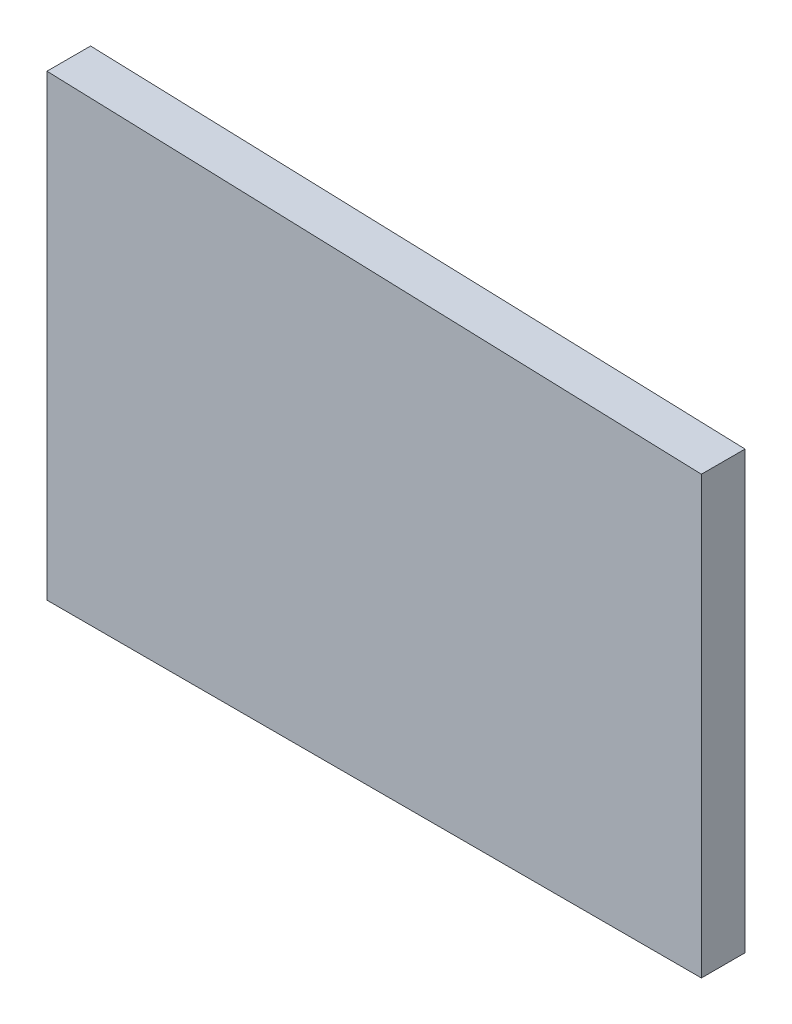
SolidWorks part; units mm, degrees
ref_plane "Ebene vorne" through (0, 0, 0) normal (0, 0, 1) x (1, 0, 0)
ref_plane "Ebene oben" through (0, 0, 0) normal (0, 1, 0) x (1, 0, 0)
ref_plane "Ebene rechts" through (0, 0, 0) normal (1, 0, 0) x (0, 0, -1)
sketch "Skizze1" plane through (0, 0, 0) normal (0, 0, 1) x (1, 0, 0)
  line L0 (0, 0) -> (0, 21)
  line L1 (0, 21) -> (30, 20)
  line L2 (30, 20) -> (30, 0)
  line L3 (30, 0) -> (0, 0)
  dimension "D1" = 30
  dimension "D2" = 20
  dimension "D3" = 21
  dimension "D4" = 90
  dimension "D5" = 90
extrude "Aufsatz-Linear austragen1" add sketch "Skizze1" along normal blind 2
sketch "Skizze2" plane through (0, 0, 2) normal (0, 0, 1) x (1, 0, 0)
  circle A0 centre (14.6667, 10.5) radius 18.0378
sketch "Skizze3" plane through (0, 0, 2) normal (0, 0, 1) x (1, 0, 0)
  line L0 (1, 1) -> (29, 1)
  line L1 (1, 1) -> (1, 19)
  line L2 (29, 1) -> (29, 19)
  line L3 (1, 19) -> (29, 19)
  line L4 (1, 1) -> (29, 19) construction
  line L5 (29, 1) -> (1, 19) construction
  line L6 (30, 0) -> (30, 20) construction
  line L7 (30, 20) -> (0, 21) construction
  point P1 (15, 10)
  point P8 (30, 10)
  point P11 (15, 20.5)
  dimension "D1" = 18
  dimension "D2" = 28
ref_point "SWASI_Vision_Point_1"
ref_point "SWASI_Vision_Point_1_helper"
ref_point "SWASI_Vision_Point_2"
ref_point "SWASI_Vision_Point_2_helper"
ref_point "SWASI_Vision_Point_3"
ref_point "SWASI_Vision_Point_3_helper"
ref_point "SWASI_Vision_Point_4"
ref_plane "SWASI_Alignment_Plane_1" through (0, 0, 0) normal (0, -1, 0) x (-1, 0, 0)
ref_plane "SWASI_Alignment_Plane_2" through (0, 0, 0) normal (0, 0, 1) x (1, 0, 0)
ref_axis "Achse1" through (30, 0, 2) along (-1, 0, 0)
ref_axis "Achse2" through (0, 0, 2) along (0.9978, 0, -0.0665)
ref_axis "Achse3" through (0, 0, 0) along (0.9978, 0, 0.0665)
ref_point "SWASI_Surface_Center_Point"
ref_axis "Achse5" through (0, 0, 2) along (0, 0, -1)
ref_axis "SWASI_Norm_Alignment_Plane_3" through (30, 0, 0) along (-1, 0, 0)
ref_plane "SWASI_Alignment_Plane_3" through (15, 0, 1) normal (-1, 0, 0) x (0, 0, 1)
ref_point "Punkt1"
ref_point "Punkt2"
ref_plane "Ebene1" through (0, 0, 2) normal (0, 0, -1) x (-1, 0, 0)
